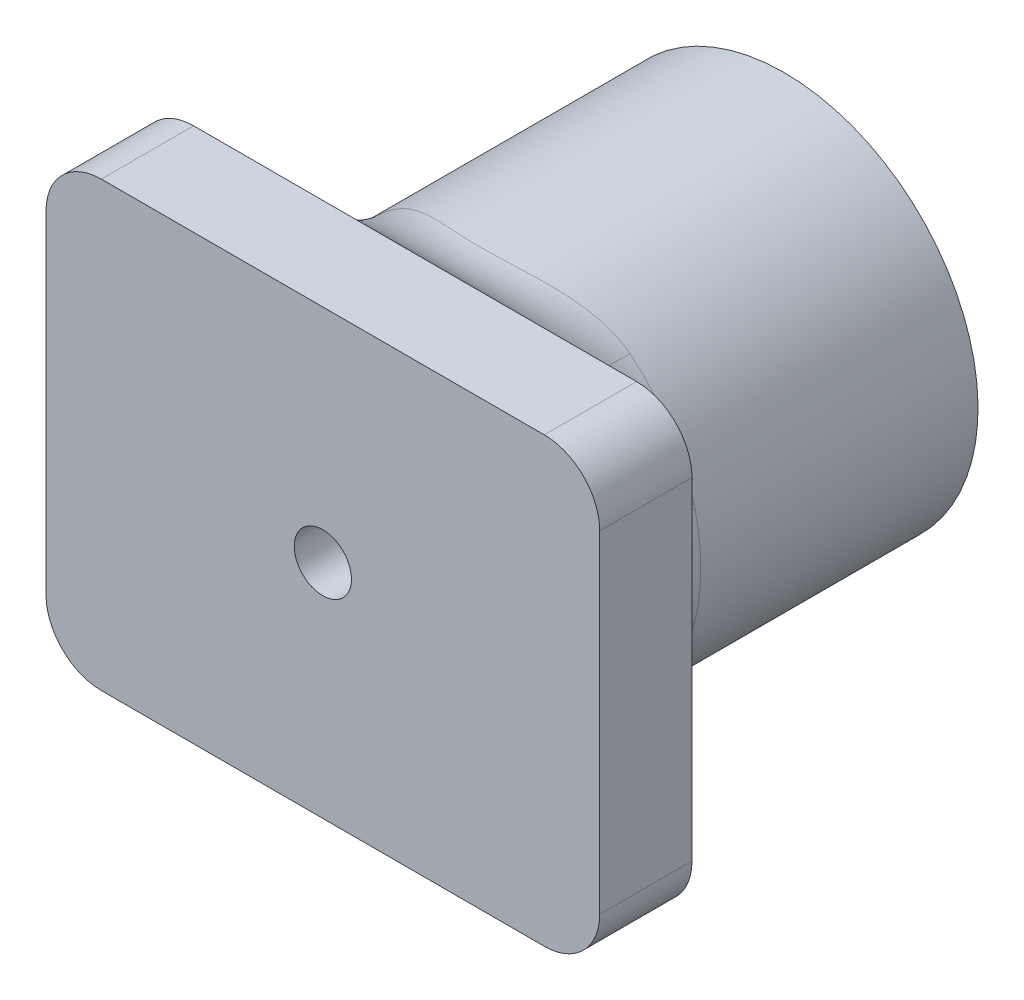
SolidWorks part; units mm, degrees
ref_plane "Front Plane" through (0, 0, 0) normal (0, 0, 1) x (1, 0, 0)
ref_plane "Top Plane" through (0, 0, 0) normal (0, 1, 0) x (1, 0, 0)
ref_plane "Right Plane" through (0, 0, 0) normal (1, 0, 0) x (0, 0, -1)
sketch "Sketch1" plane through (0, 0, 0) normal (0, 0, 1) x (1, 0, 0)
  line L1 (-15, -12) -> (15, -12)
  line L2 (-15, -12) -> (-15, 12)
  line L3 (-15, 12) -> (15, 12)
  line L4 (15, -12) -> (15, 12)
  line L5 (-15, -12) -> (15, 12) construction
  line L6 (-15, 12) -> (15, -12) construction
  circle A0 centre (0, 0) radius 1.55
  point P0 (0, 0)
  dimension "D1" = 30
  dimension "D2" = 24
extrude "Boss-Extrude1" add sketch "Sketch1" along normal blind 5
sketch "Sketch3" plane through (0, 0, 0) normal (0, 0, -1) x (-1, 0, 0)
  circle A0 centre (0, 0) radius 10.5
  circle A1 centre (0, 0) radius 8
  dimension "D1" = 16
  dimension "D2" = 21
extrude "Boss-Extrude3" add sketch "Sketch3" along normal blind 20
fillet "Fillet5" radius 3 4 edges at (-15, 12, 2.5) (-15, -12, 2.5) (15, -12, 2.5) (15, 12, 2.5)
fillet "Fillet6" radius 5 1 edges at (-10.5, 0, 0)
